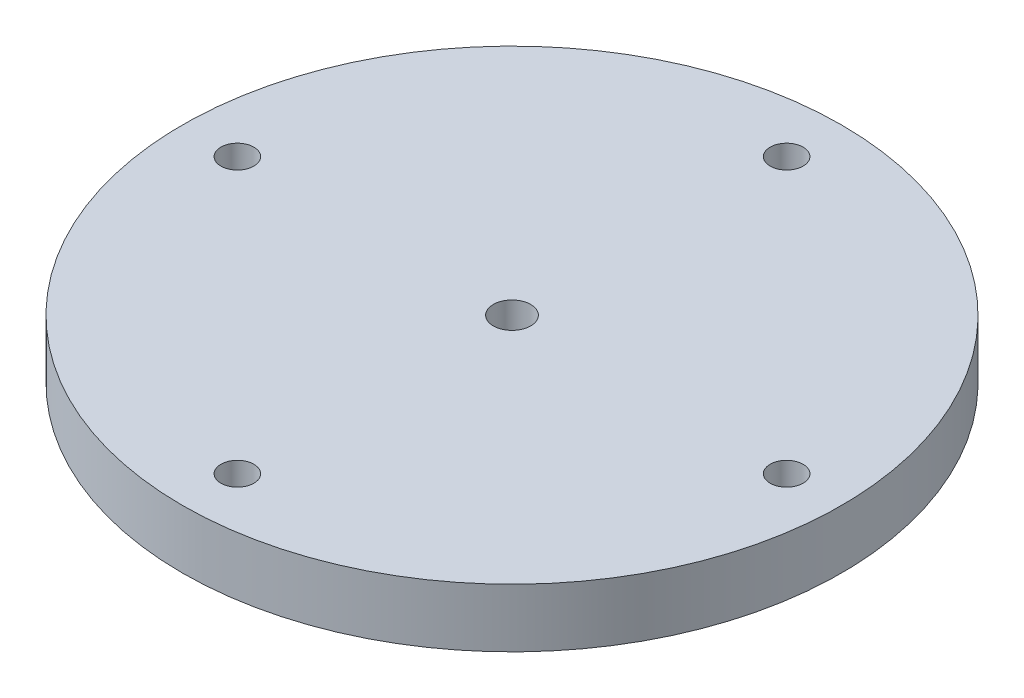
SolidWorks part; units mm, degrees
ref_plane "Front Plane" through (0, 0, 0) normal (0, 0, 1) x (1, 0, 0)
ref_plane "Top Plane" through (0, 0, 0) normal (0, 1, 0) x (1, 0, 0)
ref_plane "Right Plane" through (0, 0, 0) normal (1, 0, 0) x (0, 0, -1)
sketch "Sketch1" plane through (0, 0, 0) normal (0, 1, 0) x (1, 0, 0)
  circle A0 centre (0, 0) radius 45
  dimension "D1" = 90
extrude "Boss-Extrude1" add sketch "Sketch1" along normal blind 8
sketch "Sketch2" plane through (0, 8, 0) normal (0, 1, 0) x (1, 0, 0)
  line L0 (-1000, 0) -> (49000, 0) construction
  line L1 (0, -1000) -> (0, 49000) construction
  circle A0 centre (0, 0) radius 37.5 construction
  circle A1 centre (0, 37.5) radius 2.25
  circle A2 centre (-37.5, 0) radius 2.25
  circle A3 centre (0, -37.5) radius 2.25
  circle A4 centre (37.5, 0) radius 2.25
  circle A5 centre (0, 0) radius 45 construction
  dimension "D1" = 7.5
  dimension "D2" = 4.5
  dimension "D3" = 4.5
  dimension "D4" = 4.5
  dimension "D5" = 4.5
extrude "Cut-Extrude1" cut sketch "Sketch2" against normal through all
sketch "Sketch3" plane through (0, 8, 0) normal (0, 1, 0) x (1, 0, 0)
  circle A0 centre (0, 0) radius 2.55
  dimension "D1" = 5.1
extrude "Cut-Extrude2" cut sketch "Sketch3" against normal blind 8
